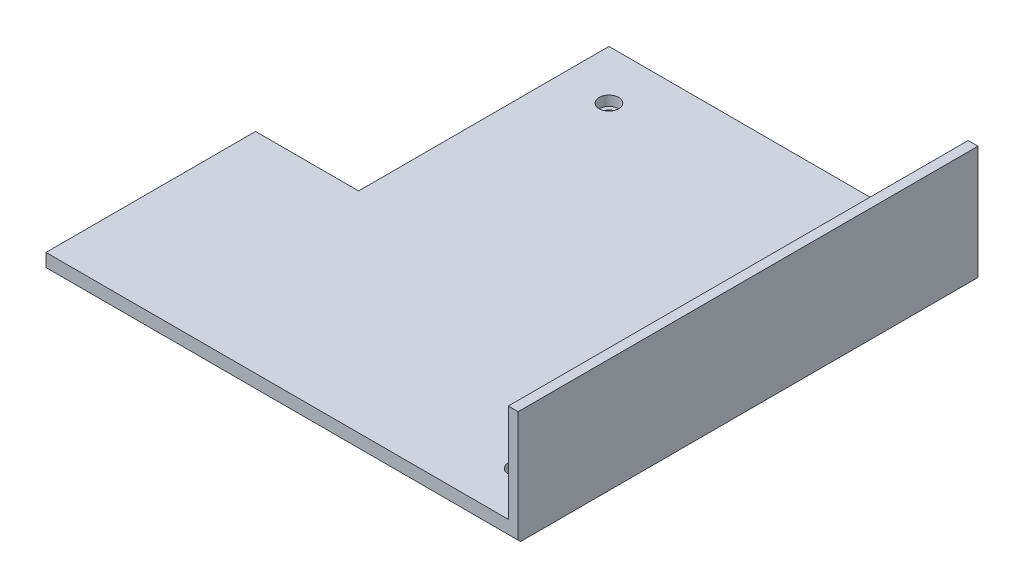
SolidWorks part; units mm, degrees
ref_plane "Front Plane" through (0, 0, 0) normal (0, 0, 1) x (1, 0, 0)
ref_plane "Top Plane" through (0, 0, 0) normal (0, 1, 0) x (1, 0, 0)
ref_plane "Right Plane" through (0, 0, 0) normal (1, 0, 0) x (0, 0, -1)
sketch "Sketch1" plane through (0, 0, 0) normal (0, 1, 0) x (1, 0, 0)
  line L1 (-96.2, 93.7) -> (96.2, 93.7)
  line L2 (-96.2, 93.7) -> (-96.2, -93.7)
  line L3 (-96.2, -93.7) -> (96.2, -93.7)
  line L4 (96.2, 93.7) -> (96.2, -93.7)
  line L5 (-96.2, 93.7) -> (96.2, -93.7) construction
  line L6 (-96.2, -93.7) -> (96.2, 93.7) construction
  point P0 (0, 0)
  dimension "D1" = 187.4
  dimension "D2" = 192.4
extrude "Boss-Extrude1" add sketch "Sketch1" along normal blind 6.35
sketch "Sketch2" plane through (0, 6.35, 0) normal (0, 1, 0) x (1, 0, 0)
  line L2 (-92.2, 89.7) -> (-92.2, -89.7)
  line L4 (96.2, -93.7) -> (96.2, 93.7)
  line L5 (96.2, 93.7) -> (-96.2, 93.7)
  line L6 (-96.2, 93.7) -> (-96.2, -93.7)
  line L7 (-96.2, -93.7) -> (96.2, -93.7)
  line L10 (-96.2, 93.7) -> (-96.2, -93.7)
  line L12 (92.2, 89.7) -> (-92.2, 89.7) construction
  line L13 (96.2, 93.7) -> (-96.2, 93.7) construction
  line L14 (92.2, -89.7) -> (92.2, 89.7) construction
  line L15 (96.2, -93.7) -> (96.2, 93.7) construction
  line L16 (-92.2, 89.7) -> (-92.2, 93.7)
  line L17 (96.2, 93.7) -> (-96.2, 93.7) construction
  line L18 (-92.2, 93.7) -> (-96.2, 93.7)
  line L22 (-92.2, -89.7) -> (92.2, -89.7) construction
  line L23 (-96.2, -93.7) -> (96.2, -93.7) construction
  line L24 (-92.2, -89.7) -> (-92.2, -93.7)
  line L25 (-96.2, -93.7) -> (96.2, -93.7) construction
  line L26 (-92.2, -93.7) -> (-96.2, -93.7)
  dimension "D1" = 0
  dimension "D2" = 4
extrude "Boss-Extrude2" add sketch "Sketch2" along normal blind 40
sketch "Sketch4" plane through (0, 6.35, 0) normal (0, 1, 0) x (1, 0, 0)
  line L0 (-92.2, -93.7) -> (96.2, -93.7) construction
  line L1 (96.2, 93.7) -> (54.2, 93.7)
  line L2 (96.2, 93.7) -> (96.2, -8.3)
  line L3 (96.2, -8.3) -> (54.2, -8.3)
  line L4 (54.2, 93.7) -> (54.2, -8.3)
  line L5 (-96.2, 93.7) -> (-96.2, -93.7) construction
  dimension "D1" = 85.4
  dimension "D2" = 150.4
extrude "Cut-Extrude1" cut sketch "Sketch4" against normal up to next
sketch "Sketch5" plane through (0, 6.35, 0) normal (0, 1, 0) x (1, 0, 0)
  line L0 (-96.2, 93.7) -> (-96.2, -93.7) construction
  line L1 (54.2, 93.7) -> (-96.2, 93.7) construction
  line L2 (54.2, 93.7) -> (54.2, 53.7) construction
  line L3 (54.2, 53.7) -> (-96.2, 53.7) construction
  line L4 (-96.2, 93.7) -> (-96.2, 53.7) construction
  line L5 (-92.2, -93.7) -> (96.2, -93.7) construction
  line L6 (-96.2, 93.7) -> (-56.2, 93.7) construction
  line L7 (-96.2, 93.7) -> (-96.2, -93.7) construction
  line L8 (-96.2, -93.7) -> (-56.2, -93.7) construction
  line L9 (-56.2, 93.7) -> (-56.2, -93.7) construction
  line L10 (-76.2, -93.7) -> (-76.2, 93.7) construction
  line L11 (54.2, 73.7) -> (-96.2, 73.7) construction
  point P18 (-76.2, 73.7)
  point P20 (-76.2, -73.7)
  point P24 (34.2, 73.7)
  dimension "D1" = 40
  dimension "D2" = 40
  dimension "D3" = 20
  dimension "D4" = 20
hole_wizard "CBORE for M4 SHCS1" positions "Sketch5" profile "Sketch6" counterbore size "M4" standard "ANSI Metric" end condition up to next
sketch "Sketch6" plane through (34.2, 6.35, -73.7) normal (1, 0, 0) x (0, 0, 1)
  line L0 (0, 0) -> (0, 6.35)
  line L1 (0, 6.35) -> (2.25, 6.35)
  line L3 (2.25, 6.35) -> (2.25, 4)
  line L4 (2.25, 4) -> (4, 4)
  line L5 (4, 4) -> (4, 0)
  line L7 (4, 0) -> (0, 0)
  line L11 (0, -6.35) -> (0, 107.95) construction
  dimension "Thru Hole Dia." = 4.5
  dimension "Thru Hole Depth" = 6.35
  dimension "C'Bore Dia." = 8
  dimension "C'Bore Depth" = 4
chamfer "Chamfer1" distance 1 angle 45 2 edges at (96.2, 0, 51) (0, 0, 93.7)
mirror "Mirror1" about plane through (96.2, 6.35, -93.7) normal (-1, 0, 0) of bodies 105
delete or keep bodies "Body-Delete/Keep 1" type delete bodies bodies 105
equation "\"D2@Sketch1\"=384.8/2"
equation "\"D2@Sketch4\"=152.4-2"
equation "\"D1@Sketch4\"=87.4-2"
